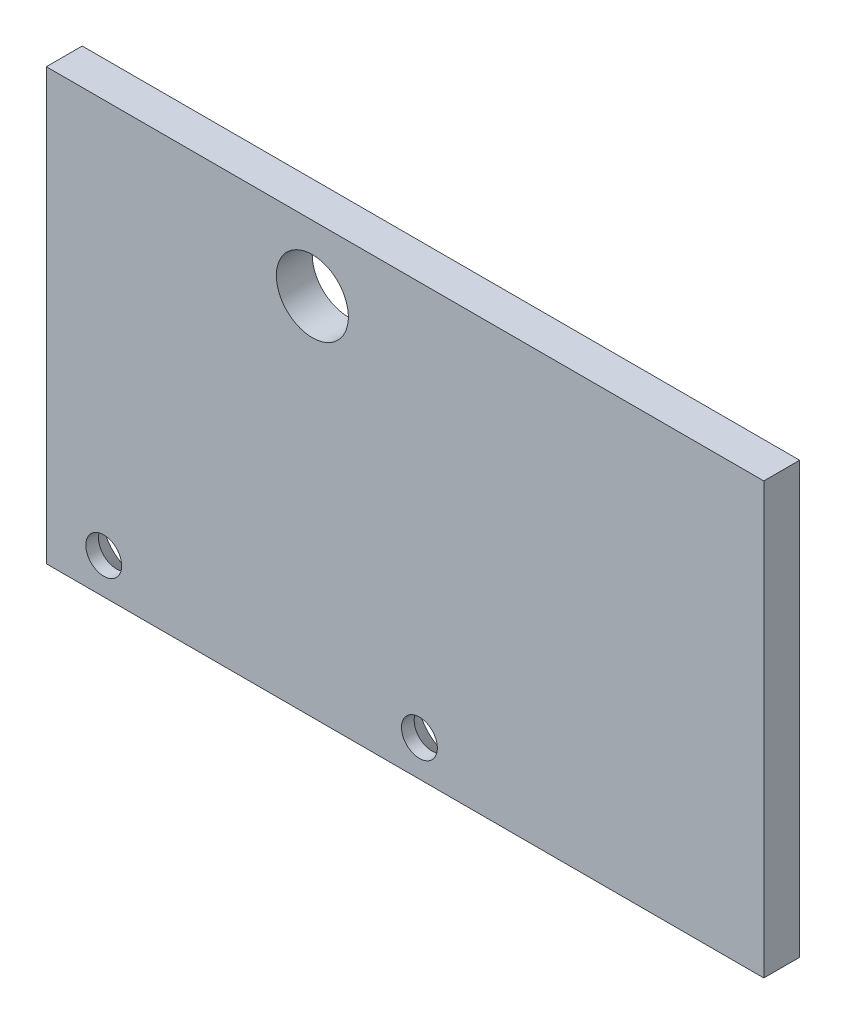
SolidWorks part; units mm, degrees
material "ABS"
ref_plane "Front Plane" through (0, 0, 0) normal (0, 0, 1) x (1, 0, 0)
ref_plane "Top Plane" through (0, 0, 0) normal (0, 1, 0) x (1, 0, 0)
ref_plane "Right Plane" through (0, 0, 0) normal (1, 0, 0) x (0, 0, -1)
sketch "Sketch1" plane through (0, 0, 0) normal (0, 0, 1) x (1, 0, 0)
  line L1 (0, 0) -> (-127, 0)
  line L2 (0, 0) -> (0, 76.2)
  line L3 (0, 76.2) -> (-127, 76.2)
  line L4 (-127, 0) -> (-127, 76.2)
  dimension "D1" = 76.2
  dimension "D2" = 127
extrude "Boss-Extrude1" add sketch "Sketch1" along normal blind 6.35
sketch "Sketch4" plane through (0, 0, 0) normal (0, 0, -1) x (-1, 0, 0)
  circle A0 centre (79.9125, 64.573) radius 6.3754
  dimension "D1" = 12.7508
extrude "Cut-Extrude1" cut sketch "Sketch4" against normal through all both and the other way through all
hole_wizard "1/4 (0.25) Diameter Hole1" positions "Sketch6" profile "Sketch8" hole size "1/4" standard "ANSI Inch" end condition through all
sketch "Sketch6" plane through (0, 0, 0) normal (0, 0, -1) x (-1, 0, 0)
  line L0 (127, 76.2) -> (127, 0) construction
  line L1 (127, 0) -> (0, 0) construction
  line L2 (50.8, 12.7) -> (50.8, 0) construction
  point P0 (116.84, 6.35)
  point P2 (60.96, 6.35)
  dimension "D1" = 10.16
  dimension "D2" = 6.35
  dimension "D3" = 6.35
  dimension "D4" = 10.16
sketch "Sketch8" plane through (-116.84, 6.35, 0) normal (1, 0, 0) x (0, 1, 0)
  line L0 (0, 0) -> (0, 6.35)
  line L1 (0, 6.35) -> (3.175, 6.35)
  line L2 (3.175, 6.35) -> (3.175, 4.1053)
  line L3 (3.175, 4.1053) -> (6.7437, 0)
  line L5 (6.7437, 0) -> (0, 0)
  line L6 (-3.175, 4.1053) -> (-6.7437, 0) construction
  line L11 (0, -6.35) -> (0, 107.95) construction
  dimension "Thru Hole Dia." = 6.35
  dimension "Thru Hole Depth" = 6.35
  dimension "Near C'Sink Dia." = 13.4874
  dimension "Near C'Sink Angle" = 82
